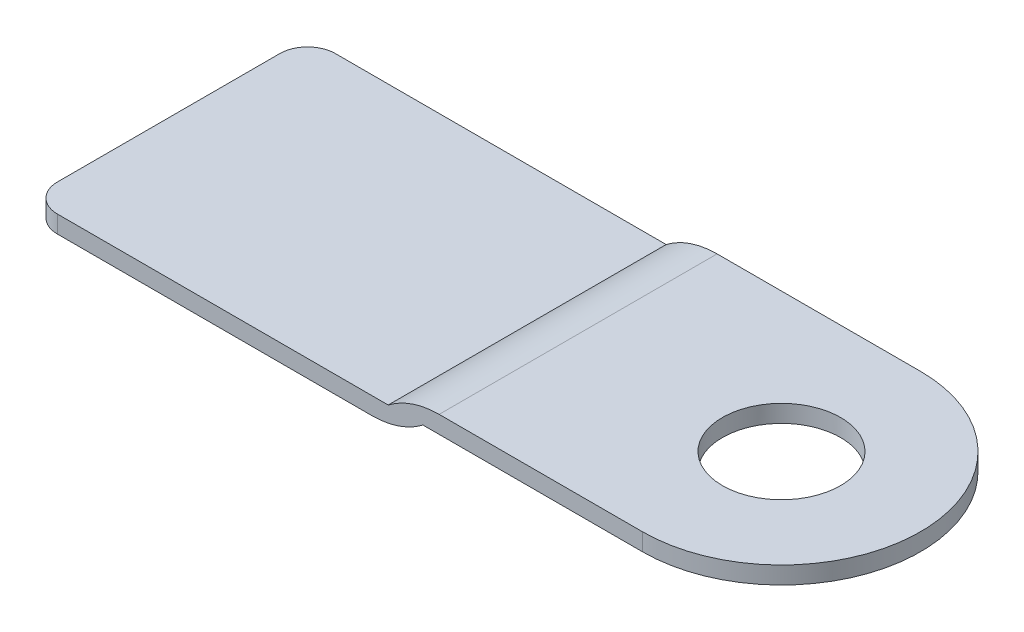
SolidWorks part; units mm, degrees
material "1.0037 (S235JR)"
ref_plane "Front Plane" through (0, 0, 0) normal (0, 0, 1) x (1, 0, 0)
ref_plane "Top Plane" through (0, 0, 0) normal (0, 1, 0) x (1, 0, 0)
ref_plane "Right Plane" through (0, 0, 0) normal (1, 0, 0) x (0, 0, -1)
sketch "Sketch1" plane through (0, 0, 0) normal (0, 0, 1) x (1, 0, 0)
  line L10 (0, 1.25) -> (-1.25, 0)
  line L11 (-27.05, 0) -> (-1.25, 0)
  line L12 (-27.05, 0) -> (-27.05, -1.25)
  line L13 (-27.05, -1.25) -> (0, -1.25)
  line L15 (1.25, 0) -> (27.05, 0)
  line L17 (0, 1.25) -> (27.05, 1.25)
  line L18 (27.05, 0) -> (27.05, 1.25)
  line L19 (0, -1.25) -> (1.25, 0)
  line L20 (0, 1.25) -> (0, -1.25) construction
  line L21 (1.25, 0) -> (-1.25, 0) construction
  dimension "D1" = 1.25
  dimension "D2" = 54.1
  dimension "D3" = 27.05
  dimension "D4" = 45
extrude "Boss-Extrude1" add sketch "Sketch1" along normal mid plane 20
fillet "Fillet1" radius 2 2 edges at (-27.05, -0.625, -10) (-27.05, -0.625, 10)
fillet "Fillet2" 2 edges at (27.05, 0.625, 10) (27.05, 0.625, -10) type full round first side face at (0.5, 0, 10) second side face at (0.5, 0, -10) middle face at (27.05, 0.625, 0)
fillet "Fillet3" radius 6 2 edges at (0, -1.25, 0) (0, 1.25, 0)
sketch "Sketch2" plane through (0, 1.25, 0) normal (0, 1, 0) x (1, 0, 0)
  circle A0 centre (17.05, 0) radius 4.25
  arc A1 (17.05, -10) -> (17.05, 10) centre (17.05, 0) ccw construction
  dimension "D1" = 8.5
extrude "Cut-Extrude1" cut sketch "Sketch2" against normal through all
